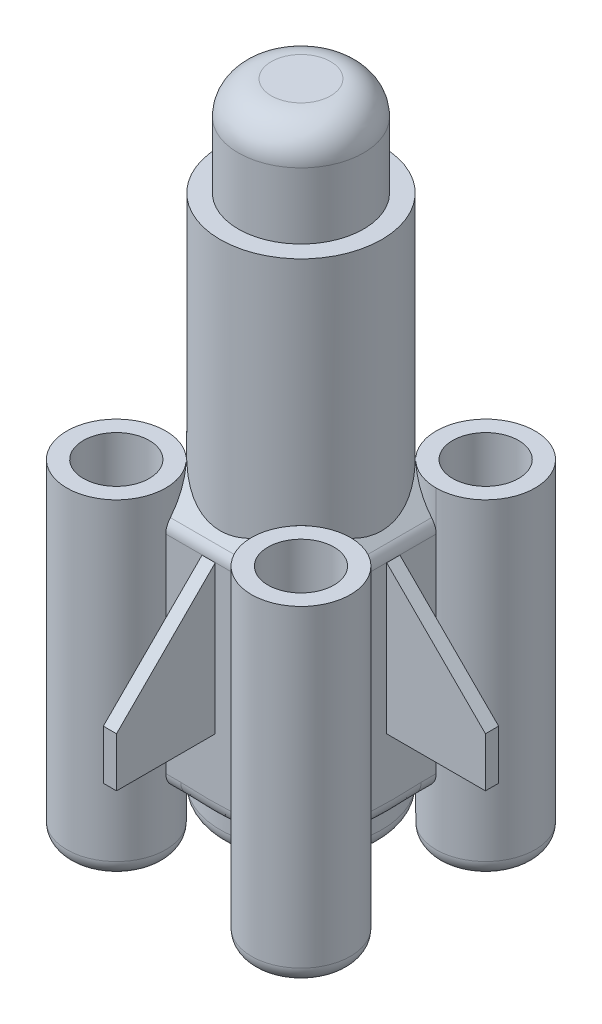
SolidWorks part; units mm, degrees
ref_plane "Plano frontal" through (0, 0, 0) normal (0, 0, 1) x (1, 0, 0)
ref_plane "Plano superior" through (0, 0, 0) normal (0, 1, 0) x (1, 0, 0)
ref_plane "Plano direito" through (0, 0, 0) normal (1, 0, 0) x (0, 0, -1)
sketch "Esboço1" plane through (0, 0, 0) normal (0, 1, 0) x (1, 0, 0)
  circle A2 centre (28, 28) radius 15
  circle A3 centre (28, -28) radius 15
  circle A4 centre (-28, -28) radius 15
  circle A5 centre (-28, 28) radius 15
  circle A6 centre (-28, 28) radius 10
  circle A7 centre (28, 28) radius 10
  circle A8 centre (28, -28) radius 10
  circle A9 centre (-28, -28) radius 10
  dimension "D3" = 30
  dimension "D7" = 30
  dimension "D8" = 30
  dimension "D11" = 30
  dimension "D12" = 20
  dimension "D13" = 20
  dimension "D14" = 20
  dimension "D15" = 20
extrude "Ressalto-extrusão1" add sketch "Esboço1" along normal blind 100 and the other way blind 0.0001
sketch "Esboço3" plane through (0, 0, 0) normal (0, 1, 0) x (1, 0, 0)
  circle A0 centre (0, 0) radius 24.5
  circle A1 centre (0, 0) radius 20
  dimension "D1" = 49
  dimension "D2" = 40
extrude "Ressalto-extrusão2" add sketch "Esboço3" along normal blind 150 from offset 10 separate body
ref_plane "Plano1" through (0, 60, 0) normal (0, 1, 0) x (1, 0, 0)
sketch "Esboço4" plane through (0, 60, 0) normal (0, 1, 0) x (1, 0, 0)
  line L0 (-28, 13) -> (-28, -13)
  line L1 (-13, -28) -> (13, -28)
  line L2 (28, -13) -> (28, 13)
  line L3 (-13, 28) -> (13, 28)
  arc A1 (13, 28) -> (28, 13) centre (28, 28) ccw
  arc A2 (-28, 13) -> (-13, 28) centre (-28, 28) ccw
  arc A3 (-13, -28) -> (-28, -13) centre (-28, -28) ccw
  arc A4 (28, -13) -> (13, -28) centre (28, -28) ccw
  circle A7 centre (0, 0) radius 20
extrude "Ressalto-extrusão3" add sketch "Esboço4" along normal mid plane 80
chamfer "Chanfro1" distance 10 angle 45 1 edges at (0, 100, -28)
fillet "Filete7" radius 5 1 edges at (0, 90, -28)
chamfer "Chanfro4" distance 10 angle 45 1 edges at (-28, 100, 0)
fillet "Filete8" radius 5 1 edges at (-28, 90, 0)
chamfer "Chanfro5" distance 10 angle 45 1 edges at (28, 100, 0)
fillet "Filete9" radius 5 1 edges at (28, 90, 0)
chamfer "Chanfro6" distance 10 angle 45 1 edges at (0, 100, 28)
fillet "Filete10" radius 5 1 edges at (0, 90, 28)
fillet "Filete11" radius 5 1 edges at (28, -0.0001, -13)
fillet "Filete12" radius 5 1 edges at (28, -0.0001, 43)
fillet "Filete13" radius 5 1 edges at (-28, -0.0001, -13)
fillet "Filete14" radius 5 1 edges at (-28, -0.0001, 43)
fillet "Filete15" radius 5 1 edges at (0, 10, 24.5)
fillet "Filete16" radius 5 1 edges at (28, 20, 0)
fillet "Filete17" radius 5 1 edges at (0, 20, 28)
fillet "Filete18" radius 5 1 edges at (-28, 20, 0)
fillet "Filete19" radius 5 1 edges at (0, 20, -28)
ref_plane "Plano2" through (0, 160, 0) normal (0, 1, 0) x (1, 0, 0)
sketch "Esboço5" plane through (0, 160, 0) normal (0, 1, 0) x (1, 0, 0)
  circle A0 centre (0, 0) radius 24.5
  dimension "D1" = 49
extrude "Ressalto-extrusão4" add sketch "Esboço5" along normal blind 10
ref_plane "Plano3" through (0, 170, 0) normal (0, 1, 0) x (1, 0, 0)
sketch "Esboço6" plane through (0, 170, 0) normal (0, 1, 0) x (1, 0, 0)
  circle A1 centre (0, 0) radius 19
  dimension "D2" = 38
extrude "Ressalto-extrusão5" add sketch "Esboço6" along normal blind 30
fillet "Filete20" radius 10 1 edges at (0, 200, 19)
sketch "Esboço7" plane through (0, -0.4133, 15.059) normal (1, 0, 0) x (0, 0, -1)
  line L0 (43, 88.3495) -> (73, 58.3495)
  line L3 (73, 58.3495) -> (73, 43.3495)
  line L4 (73, 43.3495) -> (43, 43.3495)
  line L5 (43, 43.3495) -> (43, 88.3495)
  dimension "D1" = 45
  dimension "D2" = 15
  dimension "D3" = 30
extrude "Ressalto-extrusão6" add sketch "Esboço7" along normal mid plane 4 separate body contours L5 L0 L3 L4
pattern_circular "PadrãoCircular3" count 4 over 360 about axis through (0, 0, 0) along (0, 1, 0) of bodies 110
